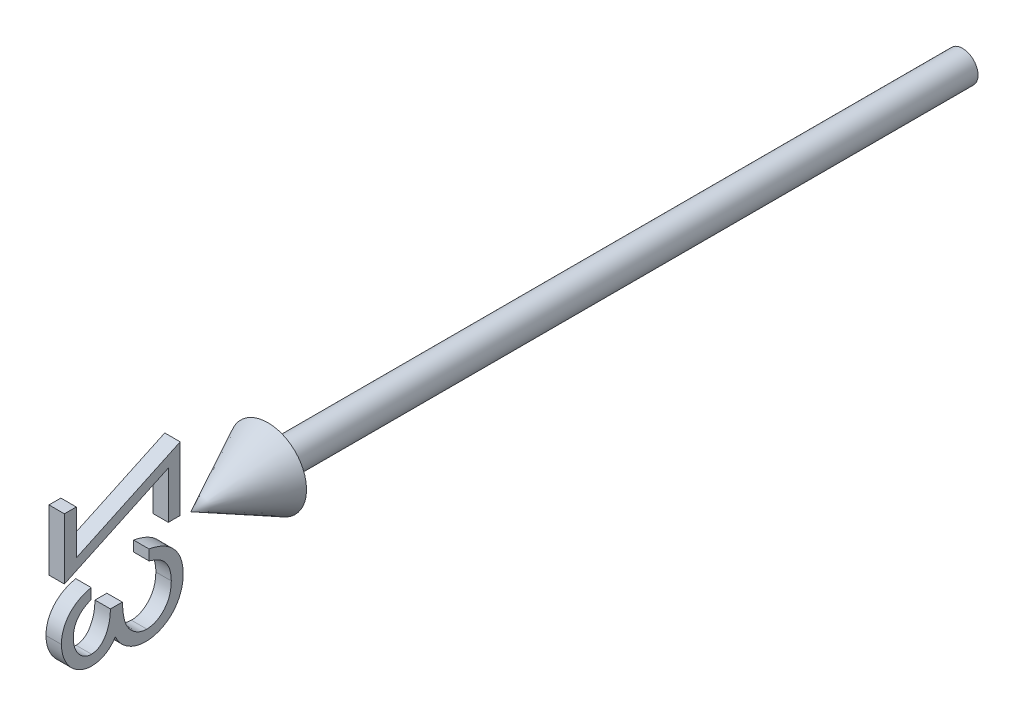
SolidWorks part; units mm, degrees
ref_plane "Front Plane" through (0, 0, 0) normal (0, 0, 1) x (1, 0, 0)
ref_plane "Top Plane" through (0, 0, 0) normal (0, 1, 0) x (1, 0, 0)
ref_plane "Right Plane" through (0, 0, 0) normal (1, 0, 0) x (0, 0, -1)
sketch "Sketch2" plane through (0, 0, 0) normal (0, 1, 0) x (1, 0, 0)
  line L0 (0, 41.95) -> (0, -114.4521) construction
  line L1 (-36.8894, 0) -> (41.4965, 0) construction
  line L2 (0, -100) -> (5, -90)
  line L3 (5, -90) -> (2, -90)
  line L4 (2, -90) -> (2, 0)
  line L5 (2, 0) -> (0, 0)
  line L6 (0, 0) -> (0, -100)
  dimension "D1" = 100
  dimension "D2" = 2
  dimension "D3" = 10
  dimension "D4" = 5
revolve "Revolve1" add sketch "Sketch2" angle 360 about L0
sketch "Sketch3" plane through (0, 0, 0) normal (1, 0, 0) x (0, -1, 0)
  line L0 (0, -101.5706) -> (0, -127.8138) construction
  line L1 (-10.1124, -102.3675) -> (14.1256, -102.3675) construction
  text T0 "Z3" font "Century Gothic" height 15
extrude "Boss-Extrude1" add sketch "Sketch3" against normal blind 1 and the other way blind 1 separate body
equation "\"frame_arrow_length\"=100"
equation "\"D1@Sketch2\"=\"frame_arrow_length\""
equation "\"frame_arrow_odA\"=4"
equation "\"D2@Sketch2\"=\"frame_arrow_odA\"/2"
equation "\"frame_arrow_head_od\"=5"
equation "\"D4@Sketch2\"=\"frame_arrow_head_od\""
equation "\"frame_arrow_head_length\"=10"
equation "\"D3@Sketch2\"=\"frame_arrow_head_length\""
equation "\"tvarobot_theta1\"=30"
equation "\"link0_ringA_odA\"= 40"
equation "\"link0_ringA_odB\"= 25"
equation "\"link0_ringA_id\"= 20"
equation "\"link0_ringA_thickness\"= (\"link0_ringA_odB\" - \"link0_ringA_id\")/2"
equation "\"link0_ringA_height\"= 3"
equation "\"link0_ringA_heightA\"= 1.5"
equation "\"link0_ringA_heightB\"=\"link0_ringA_height\"-\"link0_ringA_heightA\""
equation "\"link0_ringB_odA\"= 40"
equation "\"link0_ringB_odB\"= 29"
equation "\"link0_ringB_id\"= \"link0_shaftA_bearing_id\"+1"
equation "\"link0_ringB_thickness\"= (\"link0_ringB_odB\" - \"link0_ringB_id\")/2"
equation "\"link0_ringB_height\"= 3"
equation "\"link0_ringB_heightA\"= 1.5"
equation "\"link0_ringB_heightB\"=\"link0_ringB_height\"-\"link0_ringB_heightA\""
equation "\"link0_shaftA_bearing_od\"=27"
equation "\"link0_shaftA_bearing_id\"=20"
equation "\"link0_shaftA_thrust_bearing_od\"=35"
equation "\"link0_shaftA_thrust_bearing_id\"=20.04"
equation "\"link0_shaftA_retaining_ring_id\"=18.5"
equation "\"link0_shaftA_retaining_ring_groove_width\"=1.5"
equation "\"link0_shaftA_spline_length\"=8.0"
equation "\"link0_shaftA_spline_depth\"=1.0"
equation "\"link0_shaftA_spline_width\"=4.0"
equation "\"link0_shaftA_odA\"=\"link0_shaftA_bearing_id\""
equation "\"link0_shaftA_odB\"=35"
equation "\"link0_shaftA_odC\"=\"link0_shaftA_bearing_id\""
equation "\"link0_shaftA_odD\"=\"link0_shaftA_odC\"-2*\"link0_shaftA_spline_depth\""
equation "\"link0_shaftA_odE\"=\"link0_shaftA_bearing_id\""
equation "\"link0_shaftA_odF\"=\"link0_shaftA_odE\"-2*\"link0_shaftA_spline_depth\""
equation "\"link0_shaftA_idA\"=10"
equation "\"link0_shaftA_idB\"=6"
equation "\"link0_shaftA_length\"=39.5"
equation "\"link0_shaftA_lengthA\"=8.0"
equation "\"link0_shaftA_lengthB\"=12.0"
equation "\"link0_shaftA_lengthC\"=35.0"
equation "\"link0_shaftA_lengthD\"=39.0"
equation "\"link0_shaftA_lengthE\"=\"link0_shaftA_length\"-\"link0_shaftA_lengthD\""
equation "\"link0_shaftA_offsetX\"=11"
equation "\"link0_shaftA_offsetY\"=0"
equation "\"link0_shaftA_bolt_pattern_dia\"=14"
equation "\"link0_motor_center_dist\"=26"
equation "\"link0_46t_pulley_spline_length\"=8"
equation "\"link0_46t_pulley_spline_depth\"=\"link0_shaftA_spline_depth\"*1.025"
equation "\"link0_46t_pulley_spline_width\"=\"link0_shaftA_spline_width\"*1.05"
equation "\"link0_46t_pulley_idA\"=\"link0_shaftA_bearing_id\"*1.025"
equation "\"link0_46t_pulley_idB\"=\"link0_46t_pulley_idA\"-2*\"link0_46t_pulley_spline_depth\""
equation "\"link0_shaftB_spline_length\"=10"
equation "\"link0_shaftB_spline_depth\"=1.0"
equation "\"link0_shaftB_spline_width\"=1.25"
equation "\"link0_shaftB_length\"=7"
equation "\"link0_shaftB_lengthA\"=1.5"
equation "\"link0_shaftB_lengthB\"=2.75"
equation "\"link0_shaftB_odA\"=32"
equation "\"link0_shaftB_odB\"=22"
equation "\"link0_shaftB_odC\"=20"
equation "\"link0_shaftB_idA\"=10"
equation "\"link0_shaftB_bolt_diameter\"=19"
equation "\"link0_shaftB_bearing_od\"=27"
equation "\"link0_shaftB_bearing_id\"=20"
equation "\"link0_motor_length\"=46.5"
equation "\"link0_motor_width\"=28.5"
equation "\"link0_motor_height\"=34"
equation "\"link0_motor_offset\"=8"
equation "\"link0_shellA_thickness\"=2.5"
equation "\"link0_shellB_thickness\"=\"link0_shellA_thickness\""
equation "\"link0_plateA_shellA_height\"=48"
equation "\"link0_shellA_width\" =\"link0_plateA_width\""
equation "\"link0_shellA_height\" = \"link0_plateA_shellA_height\"-\"link0_plateA_height\""
equation "\"link0_shellA_length\" = \"link0_plateA_lengthB\" "
equation "\"link0_shellB_length\"=\"link0_shellA_length\""
equation "\"link0_shellA_radius\" = 0.375*25.4"
equation "\"link0_shellA_radiusA\"= \"link0_plateA_radiusA\""
equation "\"link0_shellA_radiusB\"= \"link0_plateA_radiusB\""
equation "\"link0_shellA_radiusC\"= 3"
equation "\"link0_postA_height\"=7"
equation "\"link0_postA_width\"=16"
equation "\"link0_postA_length\"=20"
equation "\"link0_postA_posX\"=22"
equation "\"link0_postA_posY\"=17.5"
equation "\"link0_postA_pocket_width\"=6.0"
equation "\"link0_postA_pocket_length\"=2.5"
equation "\"link0_postA_pocket_depth\"=9"
equation "\"link0_postA_pocket_posZ\"=10"
equation "\"link0_postB_height\"=7"
equation "\"link0_postB_width\"=16"
equation "\"link0_postB_length\"=20"
equation "\"link0_postB_posX\"=22"
equation "\"link0_postB_posY\"=17.5"
equation "\"link0_postB_id\"=3.0"
equation "\"link0_postB_pocket_width\"=6.0"
equation "\"link0_postB_pocket_length\"=2.5"
equation "\"link0_postB_pocket_depth\"=9"
equation "\"link0_postB_pocket_posZ\"=10"
equation "\"link0_postC_height\"=7"
equation "\"link0_postC_width\"=16"
equation "\"link0_postC_length\"=20"
equation "\"link0_postC_posX\"=22"
equation "\"link0_postC_posY\"=17.5"
equation "\"link0_postC_id\"=3.0"
equation "\"link0_postC_pocket_width\"=6.0"
equation "\"link0_postC_pocket_length\"=2.5"
equation "\"link0_postC_pocket_depth\"=9"
equation "\"link0_postC_pocket_posZ\"=10"
equation "\"link0_postD_height\"=7"
equation "\"link0_postD_width\"=16"
equation "\"link0_postD_length\"=20"
equation "\"link0_postD_posX\"=22"
equation "\"link0_postD_posY\"=17.5"
equation "\"link0_postD_id\"=3.0"
equation "\"link0_postD_pocket_width\"=6.0"
equation "\"link0_postD_pocket_length\"=3.0"
equation "\"link0_postD_pocket_depth\"=9"
equation "\"link0_postD_pocket_posZ\"=10"
equation "\"link0_postE_height\"=5"
equation "\"link0_postE_width\"=16"
equation "\"link0_postE_length\"=\"link0_plateE_lengthA\"-\"link0_lip_height\""
equation "\"link0_postE_posZ\"=22"
equation "\"link0_postE_posX\"=17.5"
equation "\"link0_postE_posY\"=22"
equation "\"link0_postE_id\"=3.0"
equation "\"link0_postE_cbore_id\"=6.5"
equation "\"link0_postE_hole_id\"=3"
equation "\"link0_postF_posZ\"=22"
equation "\"link0_postF_posX\"=17.5"
equation "\"link0_postF_posY\"=\"link0_plateB_lengthA\"+4"
equation "\"link0_postF_id\"=3.0"
equation "\"link0_postF_cbore_id\"=6.5"
equation "\"link0_postF_hole_id\"=3"
equation "\"link0_postG_posZ\"=22"
equation "\"link0_postG_posX\"=17.5"
equation "\"link0_postG_posY\"=\"link0_plateB_lengthA\"+12"
equation "\"link0_postG_id\"=3.0"
equation "\"link0_postG_cbore_id\"=6.5"
equation "\"link0_postG_hole_id\"=3"
equation "\"link0_postHIJ_posY\"=6"
equation "\"link0_postH_posX\"=28"
equation "\"link0_postH_posY\"=20"
equation "\"link0_postH_posZ\"=20"
equation "\"link0_postH_length\"=10"
equation "\"link0_postI_posX\"=28"
equation "\"link0_postI_posY\"=20"
equation "\"link0_postI_posZ\"=135"
equation "\"link0_postI_length\"=10"
equation "\"link0_postJ_posX\"=28"
equation "\"link0_postJ_posY\"=20"
equation "\"link0_postJ_posZ\"=175"
equation "\"link0_postJ_length\"=10"
equation "\"link0_postK_posX\"=28"
equation "\"link0_postK_posY\"=20"
equation "\"link0_postK_posZ\"=175"
equation "\"link0_postK_length\"=10"
equation "\"link0_postL_posX\"=28"
equation "\"link0_postL_posY\"=20"
equation "\"link0_postL_posZ\"=135"
equation "\"link0_postL_length\"=10"
equation "\"link0_postM_posX\"=28"
equation "\"link0_postM_posY\"=20"
equation "\"link0_postM_posZ\"=35"
equation "\"link0_postM_length\"=10"
equation "\"link0_plateA_lengthA\"=30"
equation "\"link0_plateA_lengthB\"=150"
equation "\"link0_plateA_lengthC\"=30"
equation "\"link0_plateA_length\"=\"link0_plateA_lengthA\"+\"link0_plateA_lengthB\"+\"link0_plateA_lengthC\""
equation "\"link0_plateA_width\"=  68"
equation "\"link0_plateA_height\"= \"link0_plateA_radiusA\""
equation "\"link0_plateA_thickness\"=\"link0_shellA_thickness\""
equation "\"link0_plateA_radius\"= 9.5"
equation "\"link0_plateA_radiusA\"= 18"
equation "\"link0_plateA_radiusB\"= 18"
equation "\"link0_plateA_radiusC\"= 3"
equation "\"link0_plateB_length\"= 40"
equation "\"link0_plateB_width\"= \"link0_plateA_width\"*1.005"
equation "\"link0_plateB_height\"= \"link0_plateA_shellA_height\"*1.005"
equation "\"link0_plateB_lengthA\"=\"link0_lip_height\"+\"link0_plateD_thickness\"+\"link0_motor_mount_thickness\""
equation "\"link0_plateB_lengthB\"=\"link0_plateB_height\"-\"link0_plateB_lengthA\""
equation "\"link0_plateB_radiusA\"= \"link0_plateA_radiusA\""
equation "\"link0_plateB_radiusB\"= \"link0_plateA_radiusB\""
equation "\"link0_plateB_radiusC\"= 3"
equation "\"link0_plateB_idA\"=\"link0_shaftA_odC\"+1"
equation "\"link0_plateB_idB\"=\"link0_shaftA_bearing_od\"-2"
equation "\"link0_plateB_idC\"=\"link0_shaftA_bearing_od\"*1.005"
equation "\"link0_plateB_idD\"=\"link0_shaftA_thrust_bearing_od\"+1 "
equation "\"link0_plateB_depthA\"=1.0"
equation "\"link0_plateB_depthB\"=2.0"
equation "\"link0_plateB_depthC\"=8"
equation "\"link0_plateB_depthD\"=\"link0_plateB_length\"-\"link0_lip_height\"-\"link0_plateD_thickness\" "
equation "\"link0_plateC_length\"=\"link0_plateB_length\""
equation "\"link0_plateC_width\"= \"link0_plateB_width\""
equation "\"link0_plateC_height\"= .1*25.4"
equation "\"link0_plateA_hole_od\" = 0.1*25.4"
equation "\"link0_plateA_hole_delx\" = 0.5*25.4"
equation "\"link0_plateA_hole_delz\" = 0.75*25.4"
equation "\"link0_plateA_hole_offx\" = 0.0*25.4"
equation "\"link0_plateA_hole_offz\" = \"link0_plateA_length\"/2"
equation "\"link0_plateB_hole_od\" = 0.1*25.4"
equation "\"link0_plateB_hole_delx\"= 0.75*25.4"
equation "\"link0_plateB_hole_delz\"= 0.75*25.4"
equation "\"link0_plateB_hole_offx\"= 0.0*25.4"
equation "\"link0_plateB_hole_offz\"= 0.0*25.4"
equation "\"link0_plateC_hole_od\"= 0.1*25.4"
equation "\"link0_plateC_hole_delx\"= 0.75*25.4"
equation "\"link0_plateC_hole_delz\"= 0.75*25.4"
equation "\"link0_plateC_hole_offx\"= 0.0*25.4"
equation "\"link0_plateC_hole_offz\"= 0.0*25.4"
equation "\"link0_plateD_height\"=\"link0_plateB_height\"-2*\"link0_shellA_thickness\""
equation "\"link0_plateD_width\"=\"link0_plateB_width\"-2*\"link0_shellA_thickness\""
equation "\"link0_plateD_thickness\"=10"
equation "\"link0_plateD_radiusA\"=\"link0_plateB_radiusA\"-\"link0_shellA_thickness\""
equation "\"link0_plateD_odA\"= .375*25.4"
equation "\"link0_plateD_odB\"= .375*25.4"
equation "\"link0_plateD_bearing_id\"=20"
equation "\"link0_plateD_bearing_od\"=27"
equation "\"link0_plateE_radiusA\"=\"link0_plateA_radiusA\""
equation "\"link0_plateE_radiusB\"=\"link0_plateA_radiusB\""
equation "\"link0_plateE_radiusC\"=8.0"
equation "\"link0_plateE_length\"=30"
equation "\"link0_plateE_lengthA\"=16"
equation "\"link0_plateE_height\"=\"link0_plateB_height\""
equation "\"link0_plateE_width\"=\"link0_plateB_width\""
equation "\"link0_plateE_odA\"=\"gantry_coupler_id\"*0.99"
equation "\"link0_plateE_idA\"=\"link0_plateE_odA\"-20.0"
equation "\"link0_plateE_spline_depth\"=\"link0_poleA_spline_depth\"*1.05"
equation "\"link0_plateE_spline_width\"=\"link0_poleA_spline_width\"*1.075"
equation "\"link0_plateE_spline_length\"=\"link0_poleA_spline_length\""
equation "\"link0_plateE_coupler_length\"=46"
equation "\"link0_lip_height\"=5.0"
equation "\"link0_lip_thickness\"=2.0"
equation "\"link0_motor_mount_thickness\"=8.0"
equation "\"link0_motor_mount_idA\"=22"
equation "\"link0_motor_mount_idB\"=\"link0_shaftB_bearing_od\"*1.005"
equation "\"link0_motor_mount_idC\"=\"link0_shaftB_bearing_od\"-2"
equation "\"link0_motor_mount_depthA\"=5.5"
equation "\"link0_motor_mount_height\"=\"link0_plateD_height\""
equation "\"link0_motor_mount_width\"=\"link0_plateD_width\""
equation "\"link0_motor_mountL_height\"=36"
equation "\"link0_motor_mountL_heightA\"=12"
equation "\"link0_motor_mountL_length\"=50"
equation "\"link0_motor_mountL_lengthA\"=36"
equation "\"gantry_coupler_od\"=25.4*2.0"
equation "\"gantry_coupler_id\"=1.645*25.4"
equation "\"gantry_coupler_offsetX\"=\"link0_plateE_width\"/2"
equation "\"link0_poleA_odA\"=20"
equation "\"link0_poleA_odB\"=36"
equation "\"link0_poleA_idA\"=\"link0_poleA_odA\"-2*\"link0_poleA_thickness\""
equation "\"link0_poleA_idB\"=(\"link0_plateE_idA\"/2+1.5*\"link0_lip_thickness\")*1.04"
equation "\"link0_poleA_thickness\"=3.5"
equation "\"link0_poleA_length\"=100"
equation "\"link0_poleA_lengthA\"=18.5"
equation "\"link0_poleA_lengthB\"=80"
equation "\"link0_poleA_gasket_thickness\"=1.5"
equation "\"link0_poleA_spline_depth\"=1.0"
equation "\"link0_poleA_spline_width\"=4.0"
equation "\"link0_poleA_spline_length\"=10.0"
equation "\"link1_plateB_length\"=30"
equation "\"link1_lip_height\"=\"link0_lip_height\""
equation "\"link0_tension_plateA_width\"=12"
equation "\"link0_tension_plateA_lengthA\"=10.5"
equation "\"link0_tension_plateB_width\"=\"link0_tension_plateA_width\""
equation "\"link0_tension_plateB_lengthA\"=\"link0_tension_plateA_lengthA\""
equation "\"link0_tension_wheelA_posZ\"=7"
equation "\"link0_tension_wheelA_posX\"=\"link0_plateD_height\"/2-\"link0_tension_plateA_lengthA\""
equation "\"link0_m2_clear_hole_id\"=2.35"
equation "\"link0_m2_insert_hole_id\"=2.5"
equation "\"link0_m2_tap_hole_id\"=1.75"
equation "\"link0_m2_nut_socket_width\"=4.25"
equation "\"link0_m2_nut_socket_depth\"=2.5"
equation "\"link0_m2_cbore_id\"=3.75"
equation "\"link0_m2_cbore_depth\"=7"
equation "\"link0_m2_5_clear_hole_id\"=2.75"
equation "\"link0_m2_5_insert_hole_id\"=2.75"
equation "\"link0_m2_5_tap_hole_id\"=2.25"
equation "\"link0_m2_5_nut_socket_width\"=5.25"
equation "\"link0_m2_5_nut_socket_depth\"=2.5"
equation "\"link0_m2_5_cbore_id\"=4.75"
equation "\"link0_m2_5_cbore_depth\"=2.5"
equation "\"link0_m2_5_insert_access_length\"=6.0"
equation "\"link0_m2_5_insert_access_width\"=3.0"
equation "\"link0_m3_clear_hole_id\"=3.25"
equation "\"link0_m3_insert_hole_id\"=3"
equation "\"link0_m3_tap_hole_id\"=2.75"
equation "\"link0_m3_nut_socket_width\"=5.75"
equation "\"link0_m3_nut_socket_depth\"=4.0"
equation "\"link0_m3_cbore_id\"=5.75"
equation "\"link0_m3_cbore_depth\"=3.5"
equation "\"link0_m3_insert_access_length\"=4.5"
equation "\"link0_m3_insert_access_width\"=3.5"
equation "\"link0_rpi_mount_height\"=6"
equation "\"link0_rpi_mount_width\"=49"
equation "\"link0_rpi_mount_length\"=58"
equation "\"link0_rpi_mount_post_od\"=6"
equation "\"link0_rpi_mount_posZ\"=72"
equation "\"link0_rpi_mount_posX\"=11.5"
equation "\"link0_mcu_mount_height\"=5"
equation "\"link0_mcu_mount_width\"=49"
equation "\"link0_mcu_mount_length\"=58"
equation "\"link0_mcu_mount_post_od\"=6"
equation "\"link0_mcu_mount_posZ\"=164"
equation "\"link0_mcu_mount_posX\"=4"
equation "\"link0_pwr_mount_height\"=4"
equation "\"link0_pwr_mount_width\"=15.75"
equation "\"link0_pwr_mount_length\"=75.75"
equation "\"link0_pwr_mount_post_od\"=6"
equation "\"link0_pwr_mount_posZ\"=75"
equation "\"link0_pwr_mount_posX\"=16"
equation "\"link0_pwr_board_height\"=6"
equation "\"link0_pwr_board_width\"=21"
equation "\"link0_pwr_board_length\"=80"
